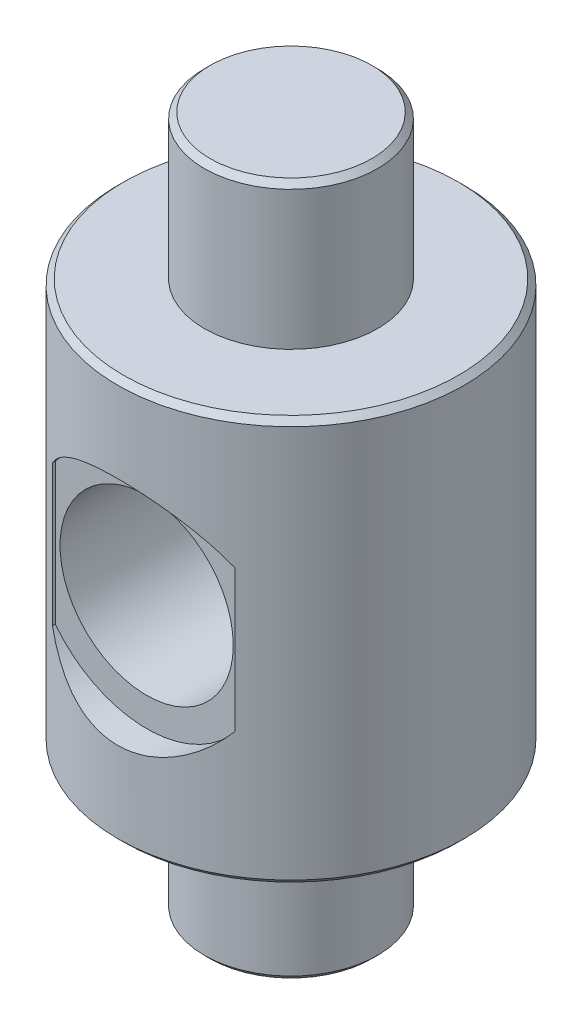
SolidWorks part; units mm, degrees
ref_plane "Front Plane" through (0, 0, 0) normal (0, 0, 1) x (1, 0, 0)
ref_plane "Top Plane" through (0, 0, 0) normal (0, 1, 0) x (1, 0, 0)
ref_plane "Right Plane" through (0, 0, 0) normal (1, 0, 0) x (0, 0, -1)
sketch "Sketch1" plane through (0, 0, 0) normal (0, 1, 0) x (1, 0, 0)
  circle A0 centre (0, 0) radius 1.5
  dimension "D1" = 3
extrude "Boss-Extrude1" add sketch "Sketch1" along normal mid plane 12
sketch "Sketch2" plane through (0, 0, 0) normal (0, 1, 0) x (1, 0, 0)
  circle A0 centre (0, 0) radius 3
  dimension "D1" = 6
extrude "Boss-Extrude2" add sketch "Sketch2" along normal mid plane 7
ref_plane "Plane1" through (0, 0, 3) normal (0, 0, 1) x (1, 0, 0)
sketch "Sketch3" plane through (0, 0, 3) normal (0, 0, 1) x (1, 0, 0)
  line L0 (1.5815, 1.2243) -> (1.5815, -1.2243)
  line L1 (0, 0) -> (0, -0.7249) construction
  line L2 (-1.5815, 1.2243) -> (-1.5815, -1.2243)
  arc A0 (-1.5815, -1.2243) -> (1.5815, -1.2243) centre (0, 0) ccw
  circle A1 centre (0, 0) radius 1.5
  arc A2 (1.5815, 1.2243) -> (-1.5815, 1.2243) centre (0, 0) ccw
  dimension "D1" = 4
  dimension "D2" = 3
extrude "Cut-Extrude1" cut sketch "Sketch3" against normal blind 0.5 contours A0 L0 A2 L2
extrude "Cut-Extrude2" cut sketch "Sketch3<3>" against normal through all contours A1 region at (0, 0, 3)
sketch "Sketch3<3>" plane through (0, 0, 3) normal (0, 0, 1) x (1, 0, 0) same geometry as "Sketch3"
mirror "Mirror1" about plane through (0, 0, 0) normal (0, 0, 1) of "Cut-Extrude1"
chamfer "Chamfer1" distance 0.1 angle 45 4 edges at (0, 6, 1.5) (0, -6, 1.5) (0, -3.5, 3) (0, 3.5, 3)
